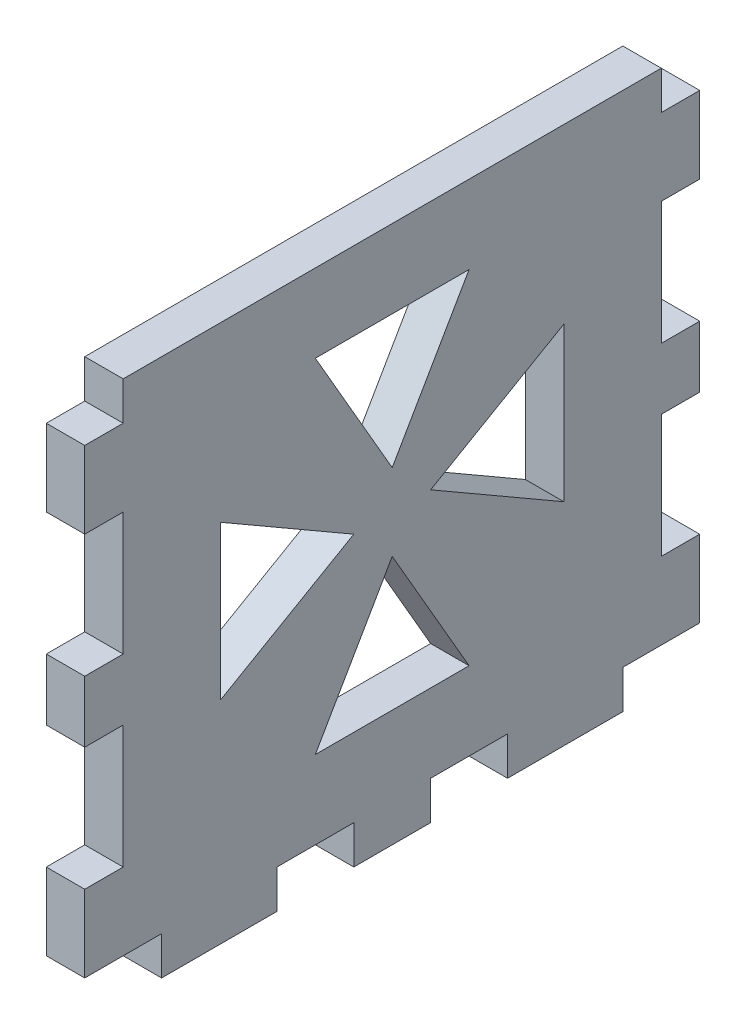
SolidWorks part; units mm, degrees
material "Pine"
ref_plane "Front Plane" through (0, 0, 0) normal (0, 0, 1) x (1, 0, 0)
ref_plane "Top Plane" through (0, 0, 0) normal (0, 1, 0) x (1, 0, 0)
ref_plane "Right Plane" through (0, 0, 0) normal (1, 0, 0) x (0, 0, -1)
sketch "Sketch1" plane through (0, 0, 0) normal (1, 0, 0) x (0, 0, -1)
  line L0 (50.8, 0) -> (50.8, 88.9) construction
  line L1 (0, 0) -> (101.6, 0)
  line L2 (0, 0) -> (0, 88.9)
  line L3 (0, 88.9) -> (101.6, 88.9)
  line L4 (101.6, 0) -> (101.6, 88.9)
  line L5 (0, 0) -> (6.35, 0)
  line L6 (0, 0) -> (0, 6.35)
  line L7 (0, 6.35) -> (6.35, 6.35)
  line L8 (6.35, 0) -> (6.35, 6.35)
  line L9 (101.6, 0) -> (95.25, 0)
  line L10 (101.6, 0) -> (101.6, 6.35)
  line L11 (101.6, 6.35) -> (95.25, 6.35)
  line L12 (95.25, 0) -> (95.25, 6.35)
  line L13 (0, 88.9) -> (6.35, 88.9)
  line L14 (0, 88.9) -> (0, 82.55)
  line L15 (0, 82.55) -> (6.35, 82.55)
  line L16 (6.35, 88.9) -> (6.35, 82.55)
  line L17 (101.6, 88.9) -> (95.25, 88.9)
  line L18 (101.6, 88.9) -> (101.6, 82.55)
  line L19 (101.6, 82.55) -> (95.25, 82.55)
  line L20 (95.25, 88.9) -> (95.25, 82.55)
  line L21 (101.6, 69.85) -> (95.25, 69.85)
  line L22 (101.6, 69.85) -> (101.6, 49.53)
  line L23 (101.6, 49.53) -> (95.25, 49.53)
  line L24 (95.25, 69.85) -> (95.25, 49.53)
  line L25 (101.6, 19.05) -> (95.25, 19.05)
  line L26 (101.6, 19.05) -> (101.6, 39.37)
  line L27 (101.6, 39.37) -> (95.25, 39.37)
  line L28 (95.25, 19.05) -> (95.25, 39.37)
  line L29 (0, 39.37) -> (6.35, 39.37)
  line L30 (6.35, 19.05) -> (6.35, 39.37)
  line L31 (0, 19.05) -> (6.35, 19.05)
  line L32 (0, 19.05) -> (0, 39.37)
  line L33 (0, 49.53) -> (6.35, 49.53)
  line L34 (6.35, 69.85) -> (6.35, 49.53)
  line L35 (0, 69.85) -> (6.35, 69.85)
  line L36 (0, 69.85) -> (0, 49.53)
  line L37 (6.35, 6.35) -> (95.25, 6.35)
  line L39 (12.7, 6.35) -> (31.75, 6.35)
  line L40 (12.7, 6.35) -> (12.7, 0)
  line L41 (12.7, 0) -> (31.75, 0)
  line L42 (31.75, 6.35) -> (31.75, 0)
  line L43 (88.9, 6.35) -> (69.85, 6.35)
  line L44 (88.9, 6.35) -> (88.9, 0)
  line L45 (88.9, 0) -> (69.85, 0)
  line L46 (69.85, 6.35) -> (69.85, 0)
  line L47 (57.15, 6.35) -> (44.45, 6.35)
  line L48 (57.15, 6.35) -> (57.15, 0)
  line L49 (57.15, 0) -> (44.45, 0)
  line L50 (44.45, 6.35) -> (44.45, 0)
  point P25 (98.425, 69.85)
  point P48 (31.75, 3.175)
  dimension "D1" = 101.6
  dimension "D2" = 88.9
  dimension "D3" = 6.35
  dimension "D4" = 6.35
  dimension "D5" = 6.35
  dimension "D6" = 6.35
  dimension "D7" = 6.35
  dimension "D8" = 6.35
  dimension "D9" = 6.35
  dimension "D10" = 6.35
  dimension "D11" = 12.7
  dimension "D12" = 12.7
  dimension "D13" = 20.32
  dimension "D14" = 20.32
  dimension "D15" = 12.7
  dimension "D16" = 12.7
  dimension "D17" = 12.7
  dimension "D18" = 12.7
  dimension "D19" = 12.7
  dimension "D20" = 19.05
extrude "Boss-Extrude1" add sketch "Sketch1" along normal blind 6.35 contours L1 L0 L3 L16 L15 L2 L35 L34 L33 L29 L30 L31 L7 L8 | L0 L1 L12 L11 L4 L25 L28 L27 L23 L24 L21 L19 L20 L3 | L40 L39 L42 L41 | L48 L47 L50 L49 | L44 L43 L46 L45 region at (0, 47.4409, -50.8)
sketch "Sketch2" plane through (6.35, 0, 0) normal (1, 0, 0) x (0, 0, -1)
  line L0 (50.8, 88.9) -> (50.8, 0) construction
  line L1 (44.45, 47.625) -> (22.453, 60.325)
  line L2 (22.453, 60.325) -> (22.453, 34.925)
  line L3 (22.453, 34.925) -> (44.45, 47.625)
  line L4 (6.35, 88.9) -> (95.25, 88.9) construction
  line L6 (50.8, 53.975) -> (63.5, 75.972)
  line L7 (101.6, 39.37) -> (101.6, 49.53) construction
  line L8 (101.6, 47.625) -> (0, 47.625) construction
  line L9 (0, 39.37) -> (0, 49.53) construction
  line L10 (63.5, 75.972) -> (38.1, 75.972)
  line L11 (38.1, 75.972) -> (50.8, 53.975)
  line L12 (57.15, 47.625) -> (79.147, 34.925)
  line L13 (79.147, 34.925) -> (79.147, 60.325)
  line L14 (79.147, 60.325) -> (57.15, 47.625)
  line L15 (50.8, 41.275) -> (38.1, 19.278)
  line L16 (38.1, 19.278) -> (63.5, 19.278)
  line L17 (63.5, 19.278) -> (50.8, 41.275)
  line L18 (57.15, 0) -> (44.45, 0) construction
  circle A0 centre (29.7853, 47.625) radius 7.3323 construction
  point P20 (50.8, 47.625)
  point P29 (50.8, 47.625)
  dimension "D1" = 6.35
  dimension "=" = 41.275
  dimension "D2" = 4
  dimension "D3" = 25.4
extrude "Cut-Extrude1" cut sketch "Sketch2" against normal up to surface (6.35 mm away) up to face at (0, 35.2778, -50.8)
